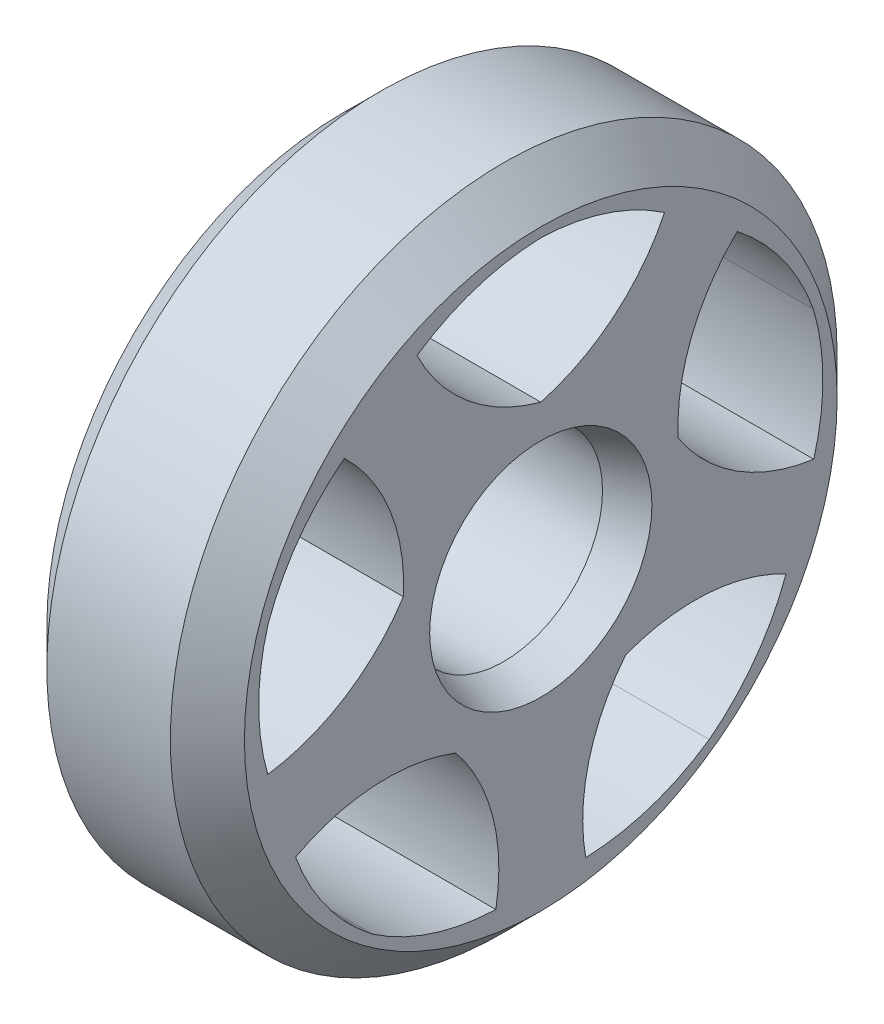
SolidWorks part; units mm, degrees
ref_plane "Front Plane" through (0, 0, 0) normal (0, 0, 1) x (1, 0, 0)
ref_plane "Top Plane" through (0, 0, 0) normal (0, 1, 0) x (1, 0, 0)
ref_plane "Right Plane" through (0, 0, 0) normal (1, 0, 0) x (0, 0, -1)
sketch "Sketch1" plane through (0, 0, 0) normal (1, 0, 0) x (0, 0, -1)
  circle A0 centre (0, 0) radius 13.5
  circle A1 centre (0, 0) radius 4
  dimension "D1" = 27
  dimension "D2" = 8
extrude "Boss-Extrude1" add sketch "Sketch1" along normal mid plane 8
sketch "Sketch2" plane through (0, 0, 0) normal (1, 0, 0) x (0, 0, -1)
  line L0 (0, 0) -> (0, 14.8201) construction
  arc A0 (0, 5.8497) -> (-5.0122, 9.994) centre (2.0377, 13.4173) cw
  arc A1 (-5.0122, 9.994) -> (0, 11.6087) centre (0.2591, 2.218) cw
  arc A2 (5.0122, 9.994) -> (0, 11.6087) centre (-0.2591, 2.218) ccw
  arc A3 (0, 5.8497) -> (5.0122, 9.994) centre (-2.0377, 13.4173) ccw
extrude "Cut-Extrude1" cut sketch "Sketch2" along normal through all both and the other way through all
pattern_circular "CirPattern1" count 5 over 360 about axis through (4, 0, 0) along (-1, 0, 0) of "Cut-Extrude1" reverse direction yes
chamfer "Chamfer1" distance 1.5 angle 45 2 edges at (4, 0, -13.5) (-4, 0, -13.5)
sketch "Sketch4" plane through (0, 0, 0) normal (1, 0, 0) x (0, 0, -1)
  circle A0 centre (0, 0) radius 13.5
  circle A1 centre (0, 0) radius 13.2
  circle A2 centre (0, 0) radius 13.5 construction
  dimension "D1" = 0.3
chamfer "Chamfer2" distance 0.5 distance2 1.5 1 edges at (4, 0, -4) first distance on face at (4, 0, -12)
equation "\"axis_diameter\"=5.66"
equation "\"padding\"=0.5"
